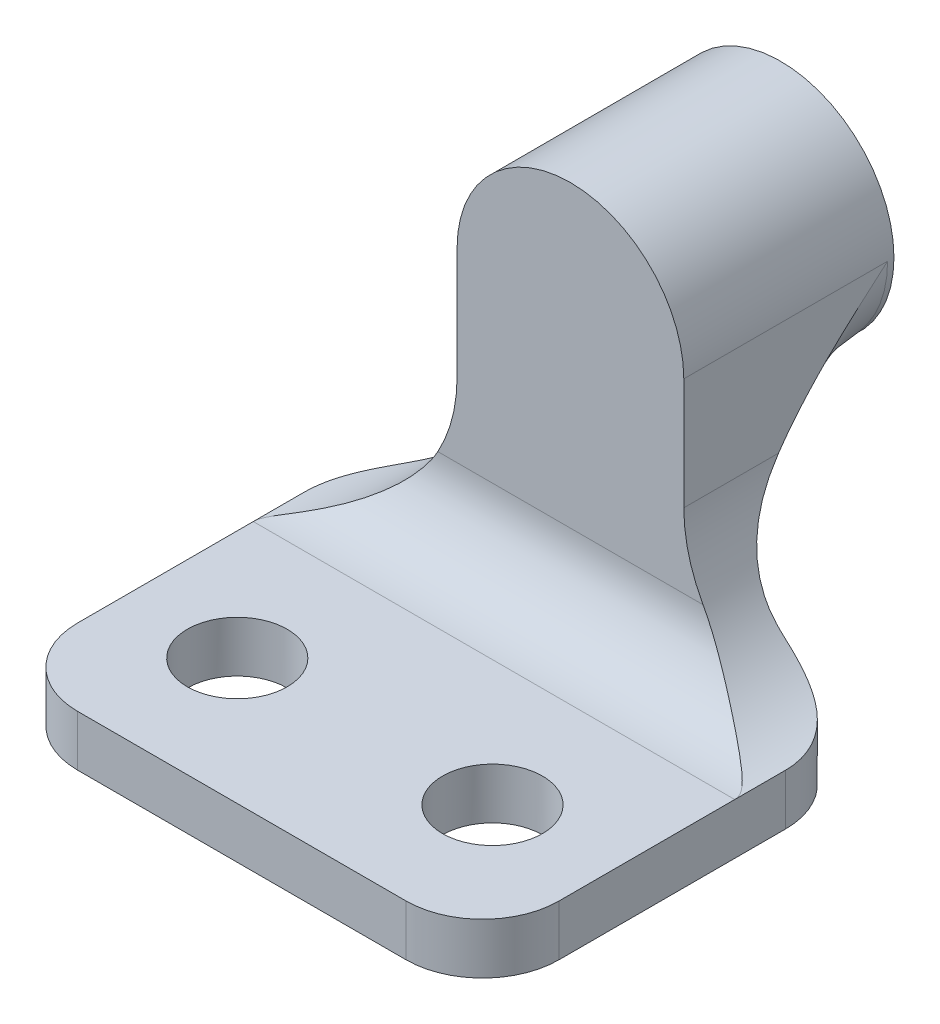
SolidWorks part; units mm, degrees
ref_plane "Alzado" through (0, 0, 0) normal (0, 0, 1) x (1, 0, 0)
ref_plane "Planta" through (0, 0, 0) normal (0, 1, 0) x (1, 0, 0)
ref_plane "Vista lateral" through (0, 0, 0) normal (1, 0, 0) x (0, 0, -1)
sketch "Croquis1" plane through (0, 0, 0) normal (0, 0, 1) x (1, 0, 0)
  circle A0 centre (0, 0) radius 4 construction
  circle A1 centre (0, 0) radius 4.381
  circle A2 centre (0, 0) radius 5.651
  dimension "D1" = 8
  dimension "D2" = 0.381
  dimension "D3" = 1.27
extrude "Saliente-Extruir1" add sketch "Croquis1" along normal mid plane 1
sketch "Croquis3" plane through (0, 0, 0.5) normal (0, 0, 1) x (1, 0, 0)
  circle A0 centre (0, 0) radius 5.651
extrude "Saliente-Extruir2" add sketch "Croquis3" along normal blind 6.937
sketch "Croquis4" plane through (0, 0, 7.437) normal (0, 0, 1) x (1, 0, 0)
  line L0 (-5.651, 0) -> (-5.651, -15.621)
  line L1 (-5.651, -15.621) -> (5.651, -15.621)
  line L2 (5.651, -15.621) -> (5.651, 0)
  circle A0 centre (0, 0) radius 5.651 construction
  arc A1 (5.651, 0) -> (-5.651, 0) centre (0, 0) ccw
  dimension "D1" = 15.621
  dimension "D2" = 11.302
extrude "Saliente-Extruir3" add sketch "Croquis4" along normal blind 2.54
fillet "Redondeo1" radius 7.62 1 edges at (0, -5.651, 7.437)
sketch "Croquis5" plane through (0, 0, 9.977) normal (0, 0, 1) x (1, 0, 0)
  line L0 (5.651, -15.621) -> (5.651, 0) construction
  line L1 (-5.651, -15.621) -> (5.651, -15.621)
  line L2 (-5.651, -15.621) -> (-5.651, -13.081)
  line L3 (-5.651, -13.081) -> (5.651, -13.081)
  line L4 (5.651, -15.621) -> (5.651, -13.081)
  dimension "D1" = 2.54
extrude "Saliente-Extruir4" add sketch "Croquis5" along normal blind 7.62
sketch "Croquis6" plane through (0, 0, 0.5) normal (0, 0, -1) x (-1, 0, 0)
  circle A0 centre (0, 0) radius 4.381
  circle A1 centre (0, 0) radius 4.381 construction
extrude "Cortar-Extruir1" cut sketch "Croquis6" against normal blind 0.5
sketch "Croquis7" plane through (0, -13.081, 0) normal (0, 1, 0) x (1, 0, 0)
  line L1 (-5.651, -17.597) -> (5.651, -17.597) construction
  line L2 (-5.651, -17.597) -> (-5.651, -7.437) construction
  line L3 (-5.651, -7.437) -> (5.651, -7.437)
  line L4 (5.651, -17.597) -> (5.651, -7.437) construction
  line L6 (5.651, -17.597) -> (5.651, -9.977) construction
  line L7 (44.2919, -7.437) -> (-31.9081, -7.437) construction
  line L8 (-5.651, -7.437) -> (-12.001, -7.437)
  line L9 (-28.695, -7.437) -> (28.455, -7.437) construction
  line L10 (-12.001, -7.437) -> (-12.001, -26.36)
  line L11 (-12.001, -26.36) -> (12.001, -26.36)
  line L12 (12.001, -26.36) -> (12.001, -7.437)
  line L13 (12.001, -7.437) -> (5.651, -7.437)
  circle A0 centre (-6.5081, -20.078) radius 5.08 construction
  circle A1 centre (6.1919, -20.0545) radius 2.4892
  circle A2 centre (-6.5081, -20.078) radius 2.4892
  circle A3 centre (-6.5081, -20.078) radius 2.4892 construction
  dimension "D1" = 10.16
  dimension "D2" = 6.35
  dimension "D3" = 6.35
  dimension "D4" = 24.002
  dimension "D5" = 18.923
extrude "Saliente-Extruir5" add sketch "Croquis7" against normal up to surface (2.54 mm away)
fillet "Redondeo2" radius 7.62 2 edges at (5.651, -13.081, 8.707) (-5.651, -13.081, 8.707)
fillet "Redondeo3" radius 3.81 1 edges at (0, -13.081, 9.977)
fillet "Redondeo4" radius 3.81 4 edges at (-12.001, -14.351, 7.437) (12.001, -14.351, 7.437) (12.001, -14.351, 26.36) (-12.001, -14.351, 26.36)
